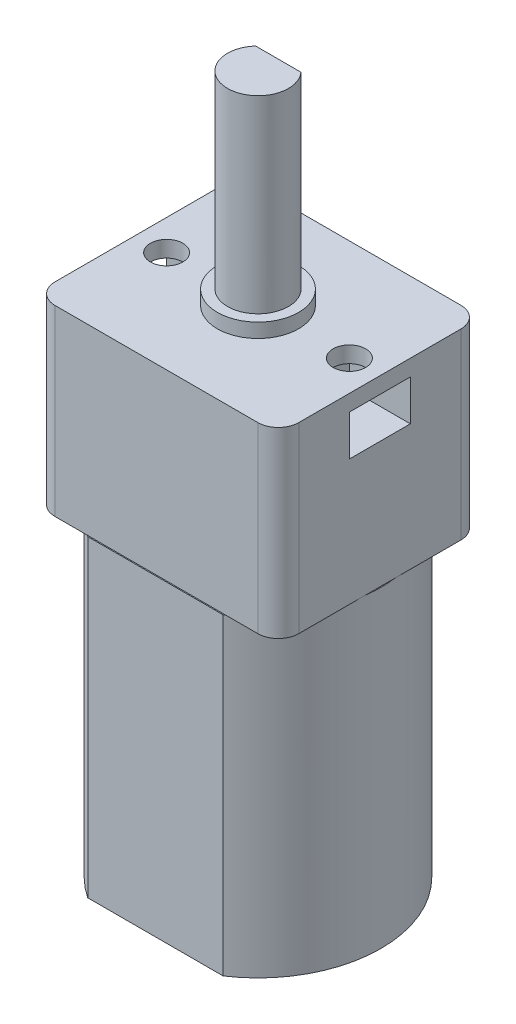
SolidWorks part; units mm, degrees
material "Brass"
ref_plane "Front" through (0, 0, 0) normal (0, 0, 1) x (1, 0, 0)
ref_plane "Top" through (0, 0, 0) normal (0, 1, 0) x (1, 0, 0)
ref_plane "Right" through (0, 0, 0) normal (1, 0, 0) x (0, 0, -1)
sketch "Gearbox base sketch" plane through (0, 0, 0) normal (0, 1, 0) x (1, 0, 0)
  line L0 (-6.6432, 3.5414) -> (-4.0925, 6.7309) construction
  line L1 (-4.9923, 5) -> (4.9923, 5)
  line L2 (-6, 3.9923) -> (-6, -3.9923)
  line L3 (-4.9923, -5) -> (4.9923, -5)
  line L4 (6, 3.9923) -> (6, -3.9923)
  line L5 (4.1123, -6.7062) -> (8.4141, -1.3269) construction
  line L6 (-5.7793, 4.6217) -> (5.7793, -4.6217) construction
  arc A0 (-4.9923, 5) -> (-6, 3.9923) centre (-4.9923, 3.9923) ccw
  arc A1 (-4.9923, -5) -> (-6, -3.9923) centre (-4.9923, -3.9923) cw
  arc A2 (6, 3.9923) -> (4.9923, 5) centre (4.9923, 3.9923) ccw
  arc A3 (6, -3.9923) -> (4.9923, -5) centre (4.9923, -3.9923) cw
  point P12 (0, 5)
  point P13 (6, 0)
  dimension "D1" = 12
  dimension "D2" = 10
  dimension "D3" = 14.8
extrude "Gearbox" add sketch "Gearbox base sketch" along normal blind 9
sketch "Axle & mount hole base sketch" plane through (0, 9, 0) normal (0, 1, 0) x (1, 0, 0)
  circle A0 centre (0, 0) radius 2
  circle A1 centre (4.5, 0) radius 0.8
  circle A2 centre (-4.5, 0) radius 0.8
  dimension "D1" = 4
  dimension "D2" = 1.6
  dimension "D4" = 1.6
  dimension "D3" = 4.5
  dimension "D5" = 4.5
extrude "Screw holes" cut sketch "Axle & mount hole base sketch" against normal blind 0.8 contours A2 | A1 region at (4.5, 9, 0) region at (-4.5, 9, 0)
sketch "Screw room base" plane through (0, 8.2, 0) normal (0, 1, 0) x (1, 0, 0)
  line L0 (-6, 3.9923) -> (-6, -3.9923) construction
  line L1 (-6, 1.5) -> (-3, 1.5)
  line L2 (-6, 1.5) -> (-6, -1.5)
  line L3 (-6, -1.5) -> (-3, -1.5)
  line L4 (-3, 1.5) -> (-3, -1.5)
  line L5 (6, -3.9923) -> (6, 3.9923) construction
  line L6 (6, 1.5) -> (3, 1.5)
  line L7 (6, 1.5) -> (6, -1.5)
  line L8 (6, -1.5) -> (3, -1.5)
  line L9 (3, 1.5) -> (3, -1.5)
  point P6 (-6, 0)
  dimension "D1" = 3
  dimension "D2" = 3
  dimension "D3" = 3
extrude "Screw room" cut sketch "Screw room base" against normal blind 2
extrude "Axle base" add sketch "Axle & mount hole base sketch<3>" along normal blind 0.7 contours A0 region at (0, 9, 0)
sketch "Axle & mount hole base sketch<3>" plane through (0, 9, 0) normal (0, 1, 0) x (1, 0, 0) same geometry as "Axle & mount hole base sketch"
sketch "Sketch4" plane through (0, 9.7, 0) normal (0, 1, 0) x (1, 0, 0)
  circle A0 centre (0, 0) radius 1.5
  dimension "D1" = 3
extrude "Axle non-notched" add sketch "Sketch4" along normal blind 0.3
sketch "Axle notched base sketch" plane through (0, 10, 0) normal (0, 1, 0) x (1, 0, 0)
  line L0 (-1.118, 1) -> (1.118, 1)
  circle A0 centre (0, 0) radius 1.5
  circle A1 centre (0, 0) radius 1.5 construction
  point P7 (0, -1.5)
  circle M1 centre (0, 0) radius 1.5
  dimension "D1" = 2.5
extrude "Axle notched" add sketch "Axle notched base sketch" along normal blind 9 contours L0 M1 region at (0, 10, 0.148)
sketch "Motor base sketch" plane through (0, 0, 0) normal (0, -1, 0) x (1, 0, 0)
  line L0 (3.3317, 5.05) -> (-3.3317, 5.05)
  line L1 (3.3317, -5.05) -> (-3.3317, -5.05)
  circle A0 centre (0, 0) radius 6.05
  line M2 (-4.9923, -5) -> (4.9923, -5)
  line M4 (6, -3.9923) -> (6, 3.9923)
  line M6 (4.9923, 5) -> (-4.9923, 5)
  line M8 (-6, 3.9923) -> (-6, -3.9923)
  dimension "D1" = 12.1
  dimension "D2" = 10.1
extrude "Motor" add sketch "Motor base sketch" along normal blind 15.4 contours A0 M2 M4 M6 M8 | A0 M8 | L1 A0 M2 | A0 L0 M6 | A0 M4 region at (0, 0, 5.0249) region at (0, 0, 0) region at (6.02, 0, 0) region at (-6.02, 0, 0) region at (0, 0, -5.0249)
sketch "Rear axle bearing & terminal base sketch" plane through (0, -15.4, 0) normal (0, -1, 0) x (1, 0, 0)
  line L1 (-3.3, 1) -> (-2.9, 1)
  line L2 (-3.3, 1) -> (-3.3, -1)
  line L3 (-3.3, -1) -> (-2.9, -1)
  line L4 (-2.9, 1) -> (-2.9, -1)
  line L5 (2.9, 1) -> (3.3, 1)
  line L6 (2.9, 1) -> (2.9, -1)
  line L7 (2.9, -1) -> (3.3, -1)
  line L8 (3.3, 1) -> (3.3, -1)
  circle A0 centre (0, 0) radius 2.5
  point P11 (-2.9, 0)
  point P12 (2.9, 0)
  point P13 (-3.1, -1)
  point P14 (3.1, -1)
  dimension "D1" = 5
  dimension "D2" = 2
  dimension "D3" = 0.4
  dimension "D4" = 2
  dimension "D5" = 0.4
  dimension "D6" = 3.1
  dimension "D7" = 3.1
extrude "Rear axle bearing" add sketch "Rear axle bearing & terminal base sketch" along normal blind 0.8 contours A0 region at (0, -15.4, 0)
extrude "Terminals" add sketch "Rear axle bearing & terminal base sketch<3>" along normal blind 1.8 contours L4 L1 L2 L3 | L8 L5 L6 L7 region at (-3.1, -15.4, 0) region at (3.1, -15.4, 0)
sketch "Rear axle bearing & terminal base sketch<3>" plane through (0, -15.4, 0) normal (0, -1, 0) x (1, 0, 0) same geometry as "Rear axle bearing & terminal base sketch"
